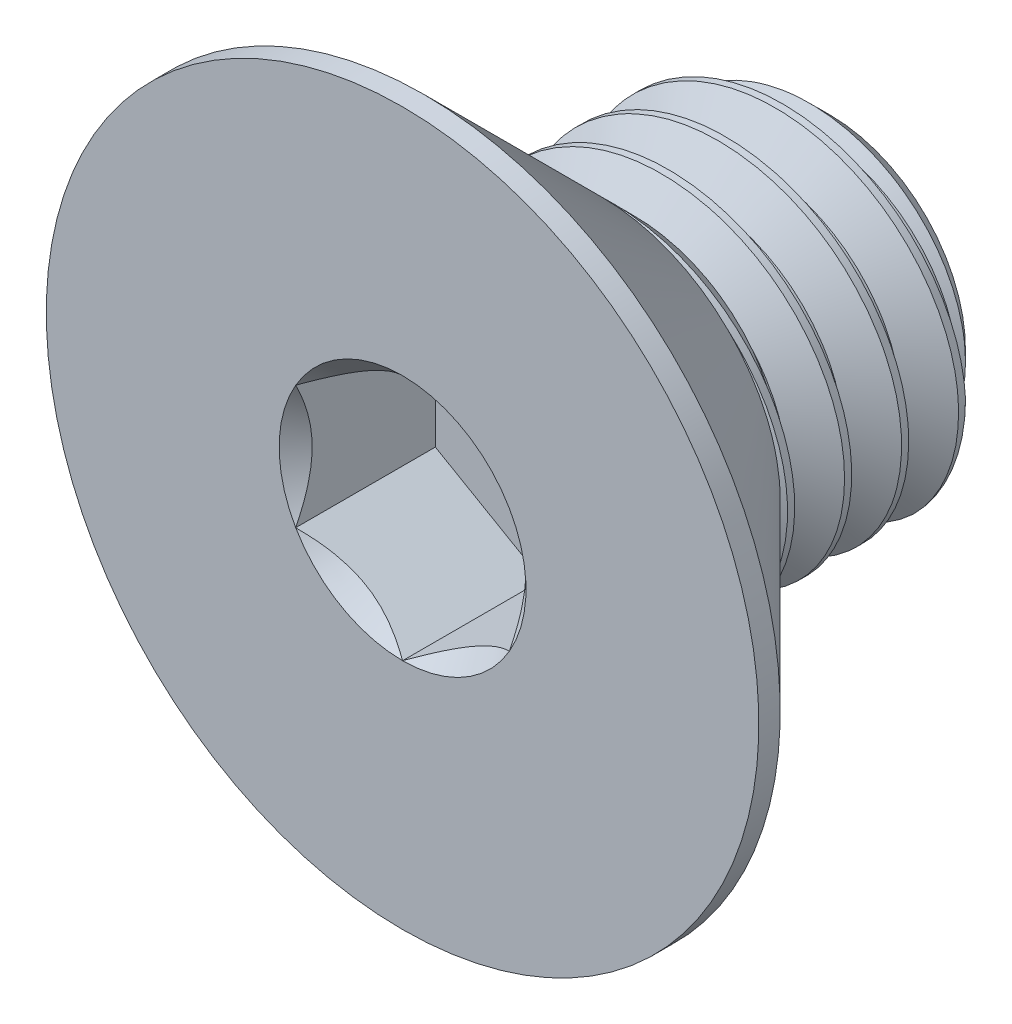
SolidWorks part; units mm, degrees
ref_plane "Front" through (0, 0, 0) normal (0, 0, 1) x (1, 0, 0)
ref_plane "Top" through (0, 0, 0) normal (0, 1, 0) x (1, 0, 0)
ref_plane "Right" through (0, 0, 0) normal (1, 0, 0) x (0, 0, -1)
sketch "Sketch1" plane through (0, 0, 0) normal (1, 0, 0) x (0, 0, -1)
  line L0 (0, 5) -> (0.3, 5) construction
  line L1 (0.3, 5) -> (2.8, 2.5) construction
  line L2 (0, 2.5) -> (6, 2.5)
  line L3 (6, 2.5) -> (6, 0)
  line L4 (6, 0) -> (0, 0)
  line L5 (0, 0) -> (0, 5) construction
  line L6 (0, 5) -> (0, -5) construction
  line L7 (6, 2.5) -> (6, -2.5) construction
  line L8 (0, -5) -> (0.3, -5) construction
  line L9 (0.3, -5) -> (2.8, -2.5) construction
  line L11 (0, 2.5) -> (0, 0)
  line L12 (2.8, 2.5) -> (2.8, 0) construction
revolve "Revolve1" add sketch "Sketch1" angle 360 mid plane about L4
sketch "Sketch3" plane through (0, 0, -6) normal (0, 0, -1) x (-1, 0, 0)
  circle A0 centre (0, 0) radius 2.5
curve "Helix/Spiral1" pitch 0.8 height 6 radius 2.5 centre (0, 0, -6) axis (0, 0, 1) start towards (0, 1, 0)
sketch "Sketch2" plane through (0, 0, 0) normal (1, 0, 0) x (0, 0, -1)
  line L0 (6, 2.5) -> (6.7, 2.5)
  line L1 (6.7, 2.5) -> (6.4, 1.9804)
  line L2 (6.4, 1.9804) -> (6.3, 1.9804)
  line L3 (6.3, 1.9804) -> (6, 2.5)
  line L4 (6.15, 2.2402) -> (6.55, 2.2402) construction
  dimension "D1" = 60
  dimension "D2" = 0.1
  dimension "D3" = 0.4
chamfer "Chamfer1" distance 0.6 angle 45 1 edges at (0, 2.5, -6)
sweep "Cut-Sweep1" cut profiles "Sketch2" path "Helix/Spiral1" align with end faces yes
sketch "Sketch7" plane through (0, 0, 0) normal (1, 0, 0) x (0, 0, -1)
  line L0 (0, 5) -> (0.3, 5) construction
  line L1 (0.3, 5) -> (2.8, 2.5) construction
  line L2 (0, 5) -> (0.3, 5)
  line L3 (0.3, 5) -> (2.8, 2.5)
  line L4 (2.8, 2.5) -> (2.8, 0) construction
  line L5 (2.8, 2.5) -> (2.8, 0)
  line L7 (0, 0) -> (0, 5) construction
  line L8 (0, 0) -> (0, 5)
  line L9 (0, 0) -> (2.8, 0)
  line L10 (5.5, 0) -> (-5.5, 0) construction
revolve "Revolve2" add sketch "Sketch7" angle 360 mid plane about L9
ref_plane "Plane1" through (0, 0, -2.8) normal (0, 0, 1) x (1, 0, 0)
sketch "Sketch8" plane through (0, 0, -2.8) normal (0, 0, 1) x (1, 0, 0)
  circle A0 centre (0, 0) radius 2.5
extrude "Boss-Extrude1" add sketch "Sketch8" against normal through all draft 45
sketch "Sketch5" plane through (0, 0, 0) normal (0, 0, 1) x (1, 0, 0)
  line L1 (1.5, -0.866) -> (1.5, 0.866)
  line L2 (1.5, 0.866) -> (0, 1.7321)
  line L3 (0, 1.7321) -> (-1.5, 0.866)
  line L4 (-1.5, 0.866) -> (-1.5, -0.866)
  line L5 (-1.5, -0.866) -> (0, -1.7321)
  line L6 (0, -1.7321) -> (1.5, -0.866)
  circle A0 centre (0, 0) radius 1.5 construction
  dimension "Hex" = 3
extrude "Cut-Extrude2" cut sketch "Sketch5" against normal blind 1.96
sketch "Sketch6" plane through (0, 0, 0) normal (0, 0, 1) x (1, 0, 0)
  circle A0 centre (0, 0) radius 1.7321
extrude "Cut-Extrude3" cut sketch "Sketch6" against normal blind 1.96 draft 45
sketch "Sketch9" [suppressed] plane through (0, 0, -5.5) normal (0, 0, 1) x (1, 0, 0)
  circle A1 centre (0, 0) radius 5
  circle A2 centre (0, 0) radius 5
  point P0 (0, 5)
  dimension "D1" = 0
extrude "Boss-Extrude2" [suppressed] add sketch "Sketch9" against normal offset from surface (18.5 mm away) 26 up to face at (0, 1.9, -6)
fillet "Fillet1" [suppressed] radius 0.5
sketch "Sketch10" plane through (0, 0, 0) normal (1, 0, 0) x (0, 0, -1)
  line L0 (6, 2.5) -> (6, -2.5) construction
  point P0 (4.8, -2.5)
  dimension "D1" = 1.2
equation "\"D3@Helix/Spiral1\" = \"Lg@Sketch1\""
equation "\"D2@Sketch2\" = \"D4@Helix/Spiral1\" * .125"
equation "\"D3@Sketch2\" = \"D4@Helix/Spiral1\" * .5"
equation "\"D1@Chamfer1\" = \"D4@Helix/Spiral1\" * .75"
equation "\"D1@Cut-Extrude2\" = \"Head Ht@Sketch1\" * .7"
equation "\"D1@Sketch10\" = \"D4@Helix/Spiral1\" * 1.5"
equation "\"D1@Cut-Extrude3\" = \"D1@Cut-Extrude2\""
equation "\"D1@Fillet1\" = \"Dia@Sketch1\" * .1"
